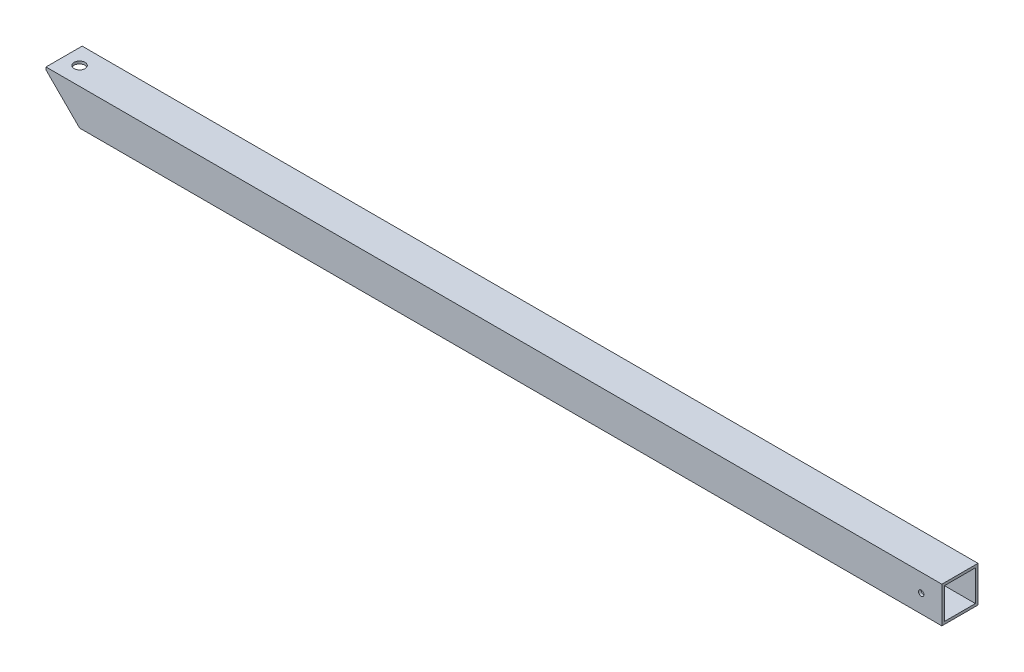
SolidWorks part; units mm, degrees
ref_plane "Front Plane" through (0, 0, 0) normal (0, 0, 1) x (1, 0, 0)
ref_plane "Top Plane" through (0, 0, 0) normal (0, 1, 0) x (1, 0, 0)
ref_plane "Right Plane" through (0, 0, 0) normal (1, 0, 0) x (0, 0, -1)
sketch "Sketch1" plane through (0, 0, 0) normal (0, 0, 1) x (1, 0, 0)
  line L1 (41.275, -44.45) -> (1101.725, -44.45)
  line L2 (1101.725, -44.45) -> (1101.725, 0)
  line L3 (1101.725, 0) -> (0, 0)
  line L4 (0, 0) -> (0, -3.175)
  line L5 (0, -3.175) -> (41.275, -44.45)
  circle A0 centre (1076.325, -22.225) radius 3.3147
  point P8 (1101.725, -22.225)
  dimension "D5" = 6.6294
  dimension "D1" = 44.45
  dimension "D2" = 3.175
  dimension "D3" = 1101.725
  dimension "D4" = 25.4
  dimension "D6" = 45
extrude "Boss-Extrude1" add sketch "Sketch1" along normal mid plane 44.45
shell "Shell1" thickness 3.175 removed face at (1079.6397, -22.225, 22.225) removed face at (1101.725, -22.225, 0) removed face at (0, -1.5875, 0) removed face at (20.6375, -23.8125, 0)
hole_wizard "1/2 Clearance Hole1" positions "Sketch2" profile "Sketch3" hole size "1/2" standard "ANSI Inch" end condition through all
sketch "Sketch2" plane through (0, 0, 0) normal (0, 1, 0) x (1, 0, 0)
  line L2 (0, -22.225) -> (0, 22.225) construction
  point P0 (19.05, 0)
  dimension "D1" = 19.05
sketch "Sketch3" plane through (19.05, 0, 0) normal (1, 0, 0) x (0, 0, 1)
  line L0 (0, 0) -> (0, 44.45)
  line L1 (0, 44.45) -> (6.7462, 44.45)
  line L2 (6.7462, 44.45) -> (6.7462, 0)
  line L5 (6.7462, 0) -> (0, 0)
  line L11 (0, -6.35) -> (0, 107.95) construction
  dimension "Thru Hole Dia." = 13.4925
  dimension "Thru Hole Depth" = 44.45
